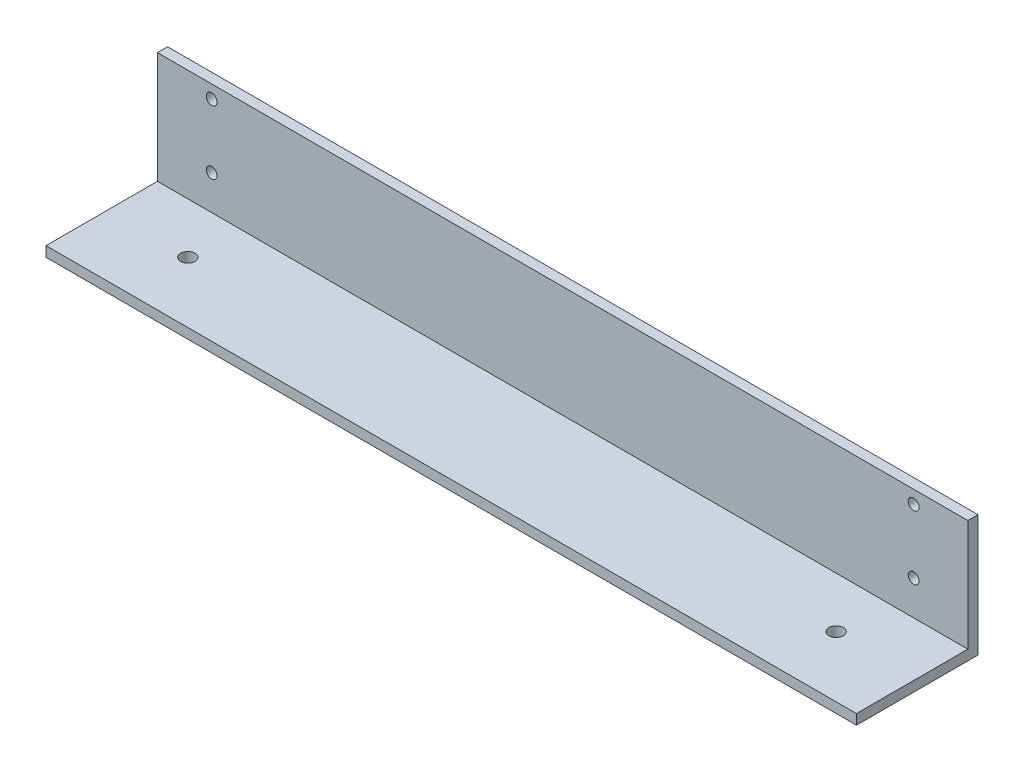
SolidWorks part; units mm, degrees
material "6061-T6 (SS)"
ref_plane "Front Plane" through (0, 0, 0) normal (0, 0, 1) x (1, 0, 0)
ref_plane "Top Plane" through (0, 0, 0) normal (0, 1, 0) x (1, 0, 0)
ref_plane "Right Plane" through (0, 0, 0) normal (1, 0, 0) x (0, 0, -1)
sketch "Sketch1" plane through (0, 0, 0) normal (1, 0, 0) x (0, 0, -1)
  line L1 (0, 0) -> (-34.925, 0)
  line L2 (0, 0) -> (0, 34.925)
  line L5 (0, 34.925) -> (3.175, 34.925)
  line L6 (-34.925, 0) -> (-34.925, -3.175)
  line L7 (-34.925, -3.175) -> (3.175, -3.175)
  line L8 (3.175, 34.925) -> (3.175, -3.175)
  dimension "D1" = 3.175
  dimension "D2" = 3.175
  dimension "D3" = 38.1
  dimension "D4" = 38.1
extrude "Boss-Extrude1" add sketch "Sketch1" along normal blind 254
hole_wizard "M3 Clearance Hole1" positions "Sketch2" profile "Sketch3" hole size "M3" standard "ANSI Metric" end condition through all
sketch "Sketch2" plane through (0, 0, 0) normal (0, 0, 1) x (1, 0, 0)
  line L0 (254, -3.175) -> (0, -3.175) construction
  line L1 (17, 10.825) -> (0, 10.825) construction
  line L2 (0, 34.925) -> (0, 0) construction
  line L4 (237, 10.825) -> (254, 10.825) construction
  line L5 (254, 34.925) -> (254, 0) construction
  point P0 (17, 30.825)
  point P2 (17, 10.825)
  point P4 (237, 10.825)
  point P6 (237, 30.825)
  dimension "D1" = 220
  dimension "D2" = 20
  dimension "D3" = 14
sketch "Sketch3" plane through (17, 30.825, 0) normal (1, 0, 0) x (0, -1, 0)
  line L0 (0, 0) -> (0, 3.175)
  line L1 (0, 3.175) -> (1.7, 3.175)
  line L2 (1.7, 3.175) -> (1.7, 0)
  line L5 (1.7, 0) -> (0, 0)
  line L11 (0, -6.35) -> (0, 107.95) construction
  dimension "Thru Hole Dia." = 3.4
  dimension "Thru Hole Depth" = 3.175
hole_wizard "#8 Clearance Hole1" positions "Sketch4" profile "Sketch5" hole size "#8" standard "ANSI Inch" end condition through all
sketch "Sketch4" plane through (0, 0, 0) normal (0, 1, 0) x (1, 0, 0)
  line L0 (254, -34.925) -> (0, -34.925) construction
  line L1 (25.4, -15.875) -> (0, -15.875)
  line L2 (0, 0) -> (0, -34.925) construction
  line L4 (228.6, -15.875) -> (254, -15.875)
  line L5 (254, 0) -> (254, -34.925) construction
  point P0 (25.4, -15.875)
  point P2 (228.6, -15.875)
  dimension "D1" = 19.05
  dimension "D2" = 203.2
sketch "Sketch5" plane through (25.4, 0, 15.875) normal (1, 0, 0) x (0, 0, 1)
  line L0 (0, 0) -> (0, 3.175)
  line L1 (0, 3.175) -> (2.2479, 3.175)
  line L2 (2.2479, 3.175) -> (2.2479, 0)
  line L5 (2.2479, 0) -> (0, 0)
  line L11 (0, -6.35) -> (0, 107.95) construction
  dimension "Thru Hole Dia." = 4.4958
  dimension "Thru Hole Depth" = 3.175
